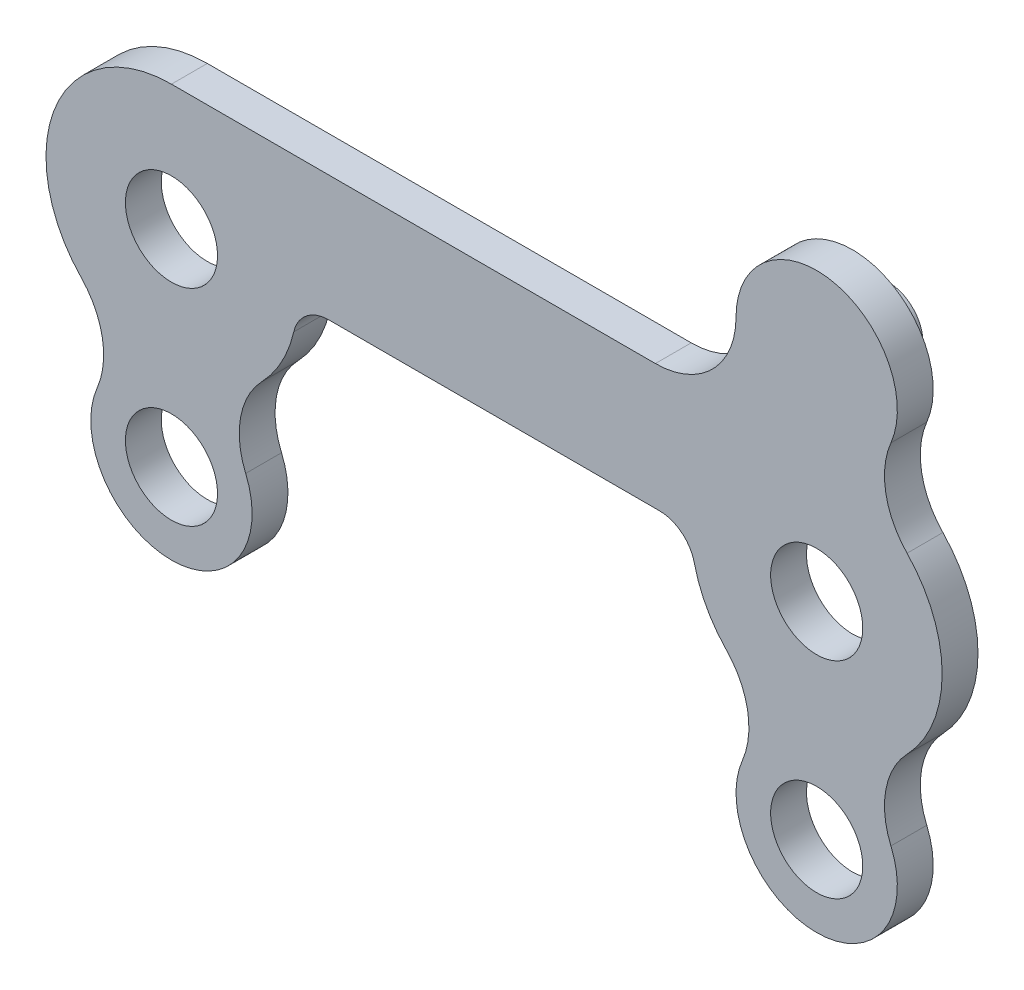
SolidWorks part; units mm, degrees
material "ABS"
ref_plane "Front Plane" through (0, 0, 0) normal (0, 0, 1) x (1, 0, 0)
ref_plane "Top Plane" through (0, 0, 0) normal (0, 1, 0) x (1, 0, 0)
ref_plane "Right Plane" through (0, 0, 0) normal (1, 0, 0) x (0, 0, -1)
sketch "Sketch1" plane through (0, 0, 0) normal (0, 0, 1) x (1, 0, 0)
  line L0 (5.5562, 0) -> (23.0188, 0)
  line L1 (0, 5.5562) -> (28.575, 5.5562)
  line L5 (0, 5.5562) -> (28.575, 5.5562) construction
  circle A0 centre (0, 0) radius 5.5562 construction
  circle A1 centre (28.575, 0) radius 5.5562 construction
  arc A2 (0, 5.5562) -> (0, -5.5562) centre (0, 0) ccw
  arc A3 (28.575, -5.5562) -> (28.575, 5.5562) centre (28.575, 0) ccw
  circle A4 centre (0, 0) radius 1.7859
  circle A5 centre (28.575, 0) radius 1.7859
  arc A6 (0, -5.5562) -> (5.5562, 0) centre (0, 0) ccw
  arc A7 (23.0188, 0) -> (28.575, -5.5562) centre (28.575, 0) ccw
  circle A10 centre (0, -9.1281) radius 3.5719
  circle A12 centre (28.575, -9.1281) radius 1.7859
  circle A15 centre (0, -9.1281) radius 1.7859
  circle A17 centre (28.575, -9.1281) radius 3.5719
  circle A27 centre (-6.5741, -6.3327) radius 3.5719
  circle A28 centre (6.5741, -6.3327) radius 3.5719
  circle A29 centre (22.0009, -6.3327) radius 3.5719
  circle A30 centre (35.1491, -6.3327) radius 3.5719
  circle A31 centre (28.575, 9.1281) radius 1.7859
  circle A32 centre (28.575, 9.1281) radius 3.5719
  circle A33 centre (21.4313, 9.1281) radius 3.5719
  circle A34 centre (35.1491, 6.3327) radius 3.5719
  dimension "D1" = 28.575
  dimension "D2" = 11.1125
  dimension "D3" = 3.5719
  dimension "D6" = 7.1437
  dimension "D7" = 3.5719
sketch "Sketch2" plane through (0, 0, 0) normal (0, 0, 1) x (1, 0, 0)
  line L0 (5.5562, 0) -> (23.0188, 0)
  line L2 (0, 5.5562) -> (28.575, 5.5562)
  circle A0 centre (0, 0) radius 5.5562
  circle A1 centre (28.575, 0) radius 5.5563
  circle A2 centre (28.575, -9.1281) radius 3.5719
  circle A3 centre (0, -9.1281) radius 3.5719
  circle A4 centre (6.5741, -6.3327) radius 3.5719
  circle A5 centre (-6.5741, -6.3327) radius 3.5719
  circle A6 centre (22.0009, -6.3327) radius 3.5719
  circle A7 centre (35.1491, -6.3327) radius 3.5719
  circle A8 centre (28.575, 9.1281) radius 3.5719
  arc A9 (0, -5.5562) -> (5.5562, 0) centre (0, 0) ccw construction
  arc A10 (23.0188, 0) -> (28.575, -5.5562) centre (28.575, 0) ccw construction
  circle A11 centre (28.575, -9.1281) radius 3.5719 construction
  circle A12 centre (0, -9.1281) radius 3.5719 construction
  circle A13 centre (22.0009, -6.3327) radius 3.5719 construction
  circle A15 centre (28.575, 9.1281) radius 3.5719 construction
  circle A16 centre (35.1491, 6.3327) radius 3.5719
  circle A18 centre (35.1491, 6.3327) radius 3.5719 construction
  circle A19 centre (0, 0) radius 2.0399
  circle A20 centre (28.575, 0) radius 2.0399
  circle A21 centre (0, -9.1281) radius 2.0399
  circle A22 centre (28.575, -9.1281) radius 2.0399
  circle A28 centre (28.575, 9.1281) radius 1.5319
  circle A30 centre (21.4313, 9.1281) radius 3.5719
  circle A31 centre (21.4313, 9.1281) radius 3.5719 construction
  dimension "D1" = 4.0799
  dimension "D2" = 4.0799
  dimension "D3" = 3.0639
extrude "Boss-Extrude1" add sketch "Sketch2" along normal blind 1.5875 contours A0 A19 | A5 A3 A0 | A4 A0 A3 | A3 A21 | A2 A22 | A6 A2 A1 | A7 A1 A2 | A1 A20 | A1 L2 A0 L0 | A30 L2 A8 | A16 A8 A1 | A8 A28 region at (14.2875, 2.9628, 0) region at (5.0072, -2.0194, 0) region at (24.7573, 3.8177, 0) region at (2.4105, -5.669, 0) region at (30.9855, 5.669, 0) region at (25.0031, 6.3541, 0) region at (26.1207, 6.6739, 0) region at (26.1645, -5.669, 0) region at (-2.4105, -5.669, 0) region at (1.9148, -6.2332, 0) region at (30.9855, -5.669, 0) region at (30.4898, -6.2332, 0)
extrude "Boss-Extrude3" add sketch "Sketch2<4>" along normal blind 1.5875 and the other way blind 1.5875 contours A28 region at (28.575, 9.1281, 0)
sketch "Sketch2<4>" plane through (0, 0, 0) normal (0, 0, 1) x (1, 0, 0) same geometry as "Sketch2"
fillet "Fillet1" radius 1.5875 2 edges at (23.0188, 0, 0.7937) (5.5562, 0, 0.7937)
